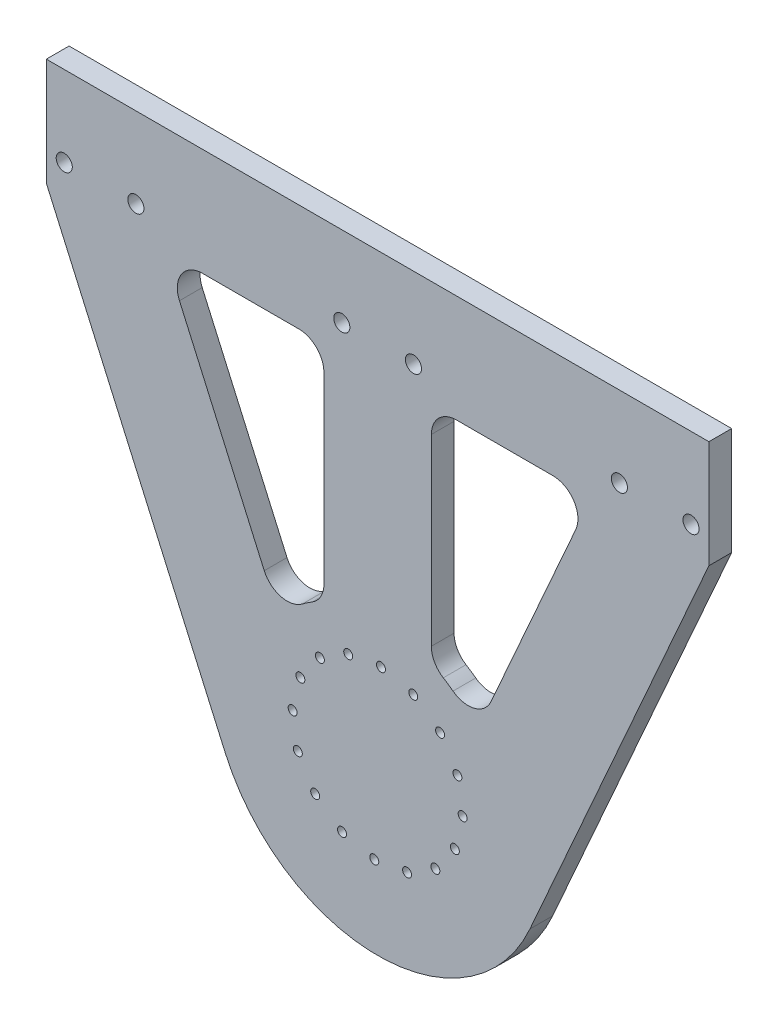
SolidWorks part; units mm, degrees
ref_plane "Front Plane" through (0, 0, 0) normal (0, 0, 1) x (1, 0, 0)
ref_plane "Top Plane" through (0, 0, 0) normal (0, 1, 0) x (1, 0, 0)
ref_plane "Right Plane" through (0, 0, 0) normal (1, 0, 0) x (0, 0, -1)
sketch "Sketch1" plane through (0, 0, 0) normal (0, 0, 1) x (1, 0, 0)
  line L1 (92.5, 124) -> (-92.5, 124)
  line L3 (0, 0) -> (0, 124) construction
  line L4 (-92.5, 124) -> (-92.5, 94)
  line L5 (-92.5, 94) -> (-42.5151, -18.834)
  line L6 (92.5, 124) -> (92.5, 94)
  line L7 (92.5, 94) -> (42.5151, -18.834)
  line L8 (42.5151, -18.834) -> (-42.5151, -18.834) construction
  line L9 (-92.5, 109) -> (92.5, 109) construction
  circle A0 centre (0, 0) radius 46.5 construction
  arc A1 (-42.5151, -18.834) -> (42.5151, -18.834) centre (0, 0) ccw
  point P16 (-92.5, 109)
  dimension "D1" = 93
  dimension "D2" = 185
  dimension "D4" = 30
  dimension "D5" = 109
extrude "Boss-Extrude1" add sketch "Sketch1" along normal mid plane 6.35
sketch "Sketch3" plane through (0, 0, -3.175) normal (0, 0, -1) x (-1, 0, 0)
  circle A0 centre (17.4402, -16.1215) radius 1.25 construction
  circle A1 centre (22.282, -8.2203) radius 1.25 construction
  circle A2 centre (9.9432, -21.5684) radius 1.25 construction
  circle A3 centre (0.9324, -23.7317) radius 1.25 construction
  circle A4 centre (-8.2203, -22.282) radius 1.25 construction
  circle A5 centre (-16.1215, -17.4402) radius 1.25 construction
  circle A6 centre (-21.5684, -9.9432) radius 1.25 construction
  circle A7 centre (-23.7317, -0.9324) radius 1.25 construction
  circle A8 centre (-22.282, 8.2203) radius 1.25 construction
  circle A9 centre (-17.4402, 16.1215) radius 1.25 construction
  circle A10 centre (-9.9432, 21.5684) radius 1.25 construction
  circle A11 centre (-0.9324, 23.7317) radius 1.25 construction
  circle A12 centre (8.2203, 22.282) radius 1.25 construction
  circle A13 centre (16.1215, 17.4402) radius 1.25 construction
  circle A14 centre (21.5684, 9.9432) radius 1.25 construction
  circle A15 centre (23.7317, 0.9324) radius 1.25 construction
  circle A16 centre (17.4402, -16.1215) radius 1.25
  circle A17 centre (22.282, -8.2203) radius 1.25
  circle A18 centre (9.9432, -21.5684) radius 1.25
  circle A19 centre (0.9324, -23.7317) radius 1.25
  circle A20 centre (-8.2203, -22.282) radius 1.25
  circle A21 centre (-16.1215, -17.4402) radius 1.25
  circle A22 centre (-21.5684, -9.9432) radius 1.25
  circle A23 centre (-23.7317, -0.9324) radius 1.25
  circle A24 centre (-22.282, 8.2203) radius 1.25
  circle A25 centre (-17.4402, 16.1215) radius 1.25
  circle A26 centre (-9.9432, 21.5684) radius 1.25
  circle A27 centre (-0.9324, 23.7317) radius 1.25
  circle A28 centre (8.2203, 22.282) radius 1.25
  circle A29 centre (16.1215, 17.4402) radius 1.25
  circle A30 centre (21.5684, 9.9432) radius 1.25
  circle A31 centre (23.7317, 0.9324) radius 1.25
extrude "Cut-Extrude2" cut sketch "Sketch3" against normal through all both and the other way through all
ref_plane "Plane1" through (0, 94, 0) normal (0, 1, 0) x (1, 0, 0)
ref_plane "Plane2" through (0, 109, 0) normal (0, 1, 0) x (1, 0, 0)
sketch "Sketch4" plane through (0, 0, -3.175) normal (0, 0, -1) x (-1, 0, 0)
  line L0 (77.5, 124) -> (77.5, 96.4275) construction
  line L1 (-92.5, 124) -> (92.5, 124) construction
  line L2 (92.5, 124) -> (92.5, 94) construction
  line L3 (0, 124) -> (0, 0) construction
  circle A0 centre (67.5, 101.5) radius 2.25
  circle A1 centre (87.5, 101.5) radius 2.25
  circle A2 centre (-87.5, 101.5) radius 2.25
  circle A3 centre (-67.5, 101.5) radius 2.25
  circle A4 centre (-10, 101.5) radius 2.25
  circle A5 centre (10, 101.5) radius 2.25
  dimension "D1" = 20
  dimension "D4" = 4.5
  dimension "D5" = 20
  dimension "D2" = 15
  dimension "D3" = 22.5
extrude "Cut-Extrude3" cut sketch "Sketch4" against normal through all
sketch "Sketch5" plane through (0, 0, -3.175) normal (0, 0, -1) x (-1, 0, 0)
  line L0 (-15, 94) -> (-59.6881, 94)
  line L1 (-15, 94) -> (-15, 31.6228)
  line L2 (-59.6881, 94) -> (-27.588, 21.5384)
  line L3 (0, 0) -> (0, 124) construction
  line L4 (-92.5, 124) -> (92.5, 124) construction
  line L5 (59.6881, 94) -> (27.588, 21.5384)
  line L6 (15, 94) -> (15, 31.6228)
  line L7 (15, 94) -> (59.6881, 94)
  line L8 (-42.5151, -18.834) -> (-92.5, 94) construction
  circle A0 centre (0, 0) radius 35 construction
  arc A1 (-27.588, 21.5384) -> (-15, 31.6228) centre (0, 0) cw
  arc A2 (15, 31.6228) -> (27.588, 21.5384) centre (0, 0) cw
  dimension "D1" = 30
  dimension "D4" = 70
  dimension "D2" = 30
  dimension "D3" = 30
extrude "Cut-Extrude4" cut sketch "Sketch5" against normal through all
fillet "Fillet1" radius 7 8 edges at (-59.6881, 94, 0) (-27.588, 21.5384, 0) (-15, 31.6228, 0) (-15, 94, 0) (15, 31.6228, 0) (27.588, 21.5384, 0) (15, 94, 0) (59.6881, 94, 0)
